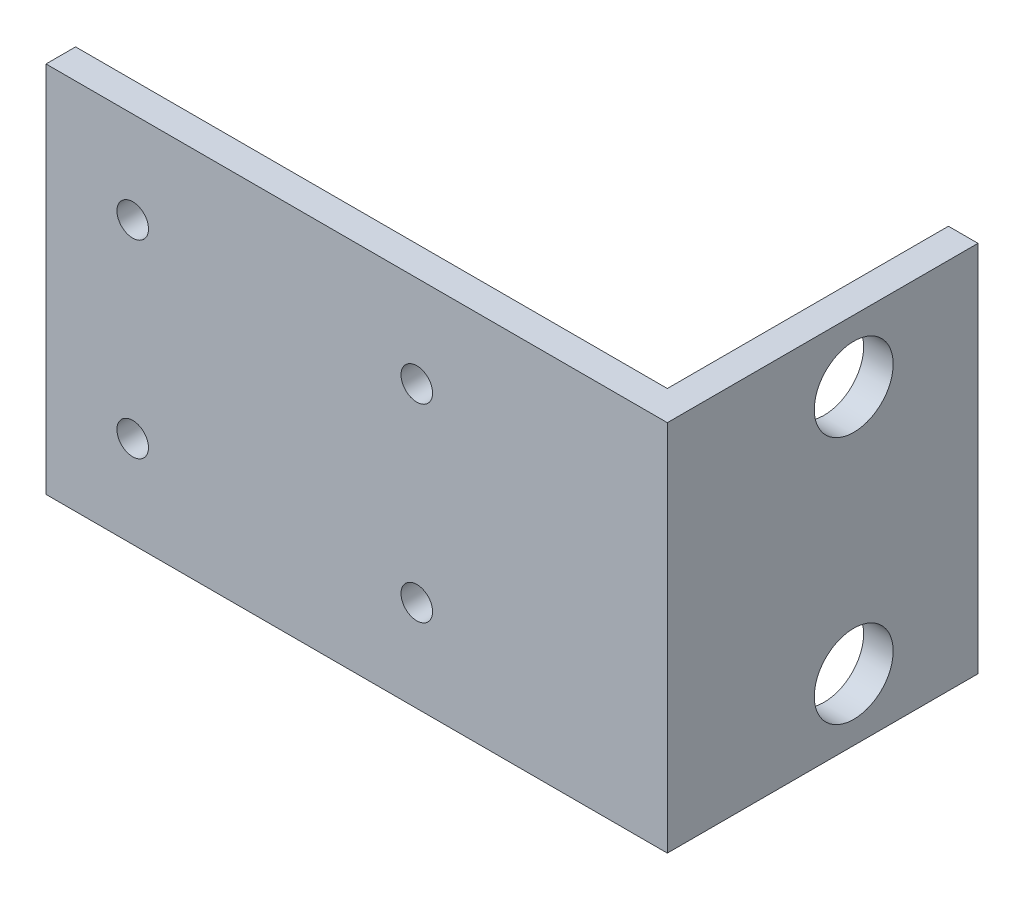
SolidWorks part; units mm, degrees
ref_plane "Front Plane" through (0, 0, 0) normal (0, 0, 1) x (1, 0, 0)
ref_plane "Top Plane" through (0, 0, 0) normal (0, 1, 0) x (1, 0, 0)
ref_plane "Right Plane" through (0, 0, 0) normal (1, 0, 0) x (0, 0, -1)
sketch "Sketch1" plane through (0, 0, 0) normal (0, 1, 0) x (1, 0, 0)
  line L0 (0, 0) -> (0, 22.6188)
  line L1 (0, 22.6188) -> (2.3813, 22.6188)
  line L2 (2.3813, 22.6188) -> (2.3813, -2.3812)
  line L3 (2.3813, -2.3812) -> (-47.6187, -2.3813)
  line L4 (-47.6187, -2.3813) -> (-47.6187, 0)
  line L5 (-47.6187, 0) -> (0, 0)
  dimension "D1" = 2.3813
  dimension "D2" = 25
  dimension "D3" = 50
extrude "Boss-Extrude1" add sketch "Sketch1" along normal blind 30
sketch "Sketch2" plane through (0, 0, 2.3812) normal (0, 0, 1) x (1, 0, 0)
  line L4 (-47.6187, 0) -> (2.3813, 0)
  line L5 (2.3813, 0) -> (2.3813, 30)
  line L6 (2.3813, 30) -> (-47.6187, 30)
  line L7 (-47.6187, 30) -> (-47.6187, 0)
  line L8 (-47.6187, 0) -> (2.3813, 0) construction
  line L9 (2.3813, 0) -> (2.3813, 30) construction
  line L10 (2.3813, 30) -> (-47.6187, 30) construction
  line L11 (-47.6187, 30) -> (-47.6187, 0) construction
  circle A0 centre (-40.64, 7.38) radius 1.27 construction
  circle A1 centre (-40.64, 7.38) radius 1.27
  circle A2 centre (-17.78, 7.38) radius 1.27 construction
  circle A3 centre (-17.78, 7.38) radius 1.27
  circle A4 centre (-17.78, 22.62) radius 1.27 construction
  circle A5 centre (-17.78, 22.62) radius 1.27
  circle A6 centre (-40.64, 22.62) radius 1.27 construction
  circle A7 centre (-40.64, 22.62) radius 1.27
  dimension "D1" = 0
extrude "Cut-Extrude1" cut sketch "Sketch2" against normal through all
sketch "Sketch3" plane through (2.3813, 0, 0) normal (1, 0, 0) x (0, 0, -1)
  line L4 (-2.3812, 0) -> (22.6188, 0)
  line L5 (22.6188, 0) -> (22.6188, 30)
  line L6 (22.6188, 30) -> (-2.3812, 30)
  line L7 (-2.3812, 30) -> (-2.3812, 0)
  line L8 (-2.3812, 0) -> (22.6188, 0) construction
  line L9 (22.6188, 0) -> (22.6188, 30) construction
  line L10 (22.6188, 30) -> (-2.3812, 30) construction
  line L11 (-2.3812, 30) -> (-2.3812, 0) construction
  circle A0 centre (12.6188, 25) radius 3.175
  circle A1 centre (12.6188, 5) radius 3.175
  point P2 (12.6188, 25)
  point P4 (12.6188, 5)
  dimension "D5" = 6.35
  dimension "D2" = 20
  dimension "D3" = 5
  dimension "D4" = 15
  dimension "D1" = 0
extrude "Cut-Extrude2" cut sketch "Sketch3" against normal through all
